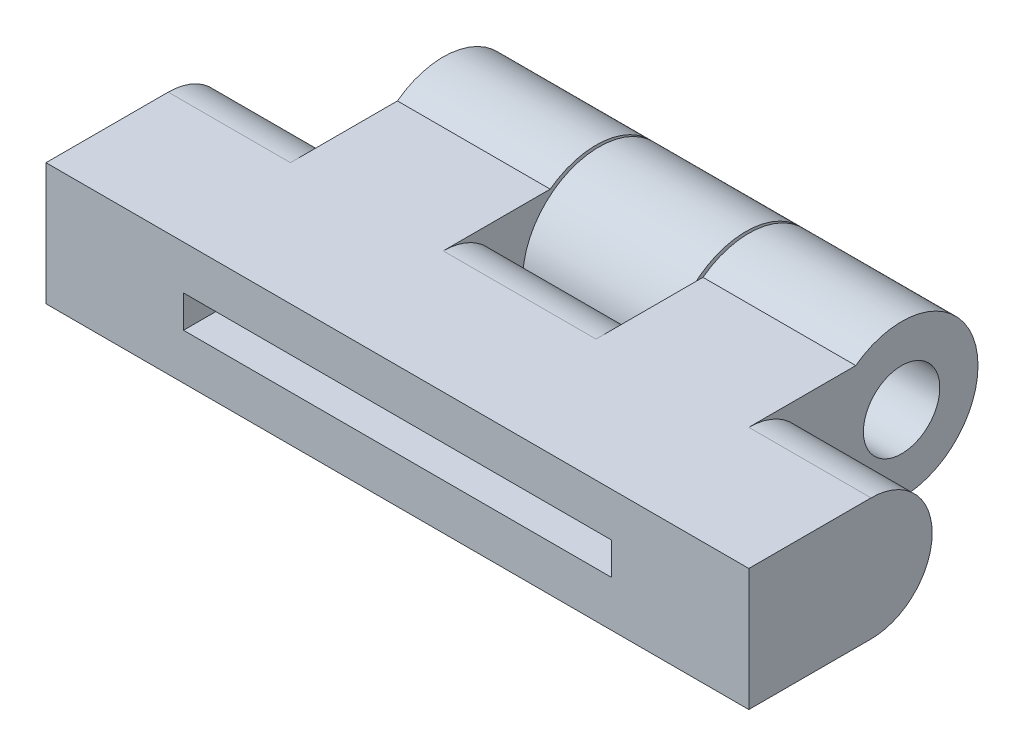
SolidWorks part; units mm, degrees
ref_plane "Front Plane" through (0, 0, 0) normal (0, 0, 1) x (1, 0, 0)
ref_plane "Top Plane" through (0, 0, 0) normal (0, 1, 0) x (1, 0, 0)
ref_plane "Right Plane" through (0, 0, 0) normal (1, 0, 0) x (0, 0, -1)
sketch "Sketch2" plane through (0, 0, 0) normal (0, 0, 1) x (1, 0, 0)
  line L1 (0, 0) -> (230, 0)
  line L2 (0, 0) -> (0, 40)
  line L3 (0, 40) -> (230, 40)
  line L4 (230, 0) -> (230, 40)
extrude "Boss-Extrude1" add sketch "Sketch2" along normal blind 80
ref_plane "Plane1" through (115, 0, 0) normal (1, 0, 0) x (0, 0, -1)
ref_plane "Plane2" through (140, 0, 0) normal (1, 0, 0) x (0, 0, -1)
sketch "Sketch20" plane through (0, 0, 80) normal (0, 0, 1) x (1, 0, 0)
  line L0 (115, -22) -> (115, 22) construction
  line L1 (45, 25.5871) -> (185, 25.5871)
  line L2 (45, 25.5871) -> (45, 15)
  line L3 (45, 15) -> (185, 15)
  line L4 (185, 25.5871) -> (185, 15)
  line L5 (45, 25.5871) -> (185, 15) construction
  line L6 (45, 15) -> (185, 25.5871) construction
  point P0 (115, 20.2935)
extrude "Cut-Extrude7" cut sketch "Sketch20" against normal blind 40
sketch "Sketch6" plane through (140, 0, 0) normal (1, 0, 0) x (0, 0, -1)
  circle A0 centre (10, 20) radius 25
extrude "Boss-Extrude3" add sketch "Sketch6" along normal blind 50 contours A0
sketch "Sketch7" plane through (140, 0, 0) normal (-1, 0, 0) x (0, 0, 1)
  circle A0 centre (-10, 20) radius 12.5
extrude "Cut-Extrude2" cut sketch "Sketch7" against normal blind 50
sketch "Sketch8" plane through (140, 0, 0) normal (-1, 0, 0) x (0, 0, 1)
  circle A0 centre (-10, 20) radius 26.5
extrude "Cut-Extrude3" cut sketch "Sketch8" along normal blind 25
sketch "Sketch11" plane through (190, 0, 0) normal (1, 0, 0) x (0, 0, -1)
  circle A0 centre (10, 20) radius 26.5
extrude "Cut-Extrude4" cut sketch "Sketch11" along normal blind 40
mirror "Mirror1" about plane through (115, 0, 0) normal (1, 0, 0) of "Cut-Extrude4", "Cut-Extrude3", "Cut-Extrude2", "Boss-Extrude3"
sketch "Sketch12" plane through (230, 0, 0) normal (1, 0, 0) x (0, 0, -1)
  line L0 (-80, 0) -> (-80, 40) construction
  line L1 (-80, 20) -> (-16.4749, 20)
  line L2 (-80, 20) -> (-80, 0)
  line L3 (-80, 0) -> (-16.4749, 0)
  line L4 (-16.4749, 20) -> (-16.4749, 0)
  line L5 (-80, 0) -> (-7.3853, 0) construction
ref_plane "Plane3" through (65, 0, 0) normal (1, 0, 0) x (0, 0, -1)
ref_plane "Plane4" through (165, 0, 0) normal (-1, 0, 0) x (0, 0, 1)
sketch "Sketch14" plane through (90, 0, 0) normal (1, 0, 0) x (0, 0, -1)
  line L0 (-80, 0) -> (-16.4749, 0) construction
  line L1 (-7.3853, 40) -> (-20, 40)
  line L2 (-7.3853, 40) -> (-7.3853, 0)
  line L3 (-7.3853, 0) -> (-20, 0)
  line L4 (-20, 40) -> (-20, 0)
extrude "Cut-Extrude6" cut sketch "Sketch14" along normal blind 50
fillet "Fillet3" radius 20 2 edges at (115, 40, 20) (115, 0, 20)
mirror "Mirror5" about plane through (165, 0, 0) normal (-1, 0, 0) of "Cut-Extrude6", "Fillet3"
mirror "Mirror8" about plane through (65, 0, 0) normal (1, 0, 0) of "Fillet3", "Cut-Extrude6"
ref_plane "Plane5" through (91, 0, 0) normal (1, 0, 0) x (0, 0, -1)
sketch "Sketch21" plane through (91, 0, 0) normal (1, 0, 0) x (0, 0, -1)
  circle A0 centre (10, 20) radius 25
extrude "Boss-Extrude5" add sketch "Sketch21" along normal blind 48 separate body
sketch "Sketch22" plane through (91, 0, 0) normal (1, 0, 0) x (0, 0, -1)
  circle A0 centre (10, 20) radius 12.5
extrude "Cut-Extrude8" cut sketch "Sketch22" along normal blind 48
